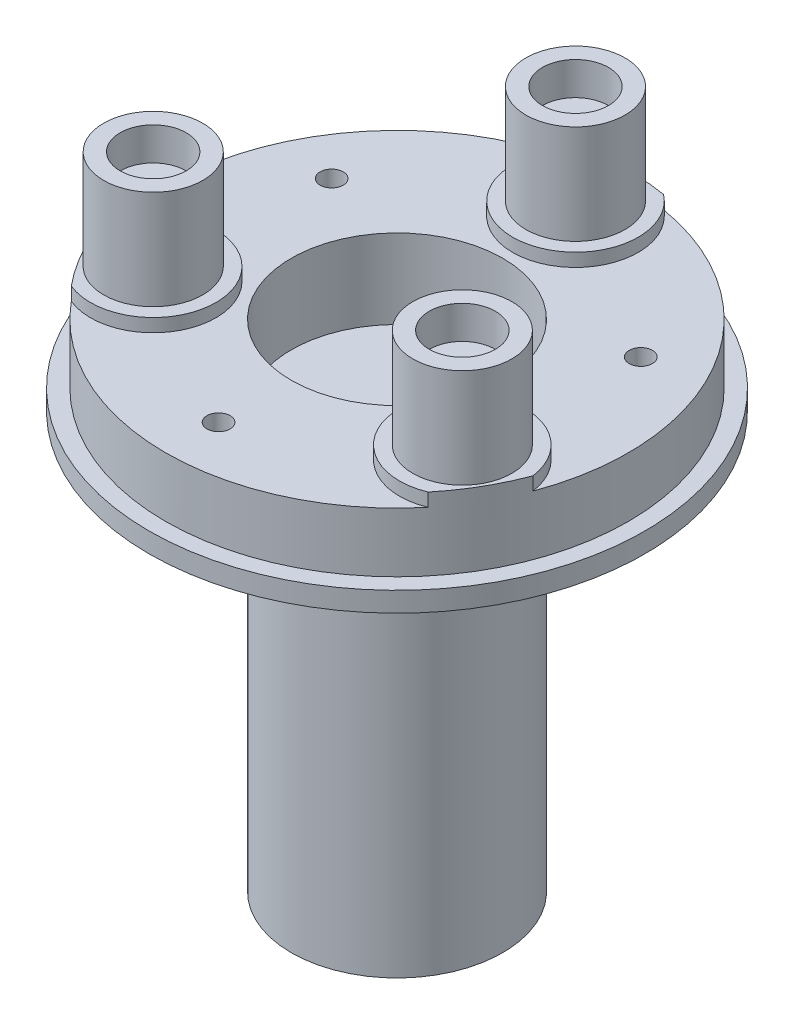
SolidWorks part; units mm, degrees
note: The reader was unsure of these and kept them because the rebuilt part matched: shared geometry of "Sketch1<3>".
ref_plane "Front Plane" through (0, 0, 0) normal (0, 0, 1) x (1, 0, 0)
ref_plane "Top Plane" through (0, 0, 0) normal (0, 1, 0) x (1, 0, 0)
ref_plane "Right Plane" through (0, 0, 0) normal (1, 0, 0) x (0, 0, -1)
sketch "Sketch1" plane through (0, 0, 0) normal (0, 1, 0) x (1, 0, 0)
  line L0 (0, 0) -> (0, 44.6523) construction
  circle A4 centre (0, 0) radius 37.5
  circle A5 centre (0, 0) radius 35
  arc A6 (-10.4425, 33.4059) -> (10.4425, 33.4059) centre (0, 30) ccw
  circle A7 centre (0, 0) radius 35
  arc A8 (34.1516, -7.6594) -> (23.7091, -25.7465) centre (25.9808, -15) ccw
  arc A9 (-23.7091, -25.7465) -> (-34.1516, -7.6594) centre (-25.9808, -15) ccw
  point P17 (0, 0)
  dimension "D1" = 75
  dimension "D2" = 70
  dimension "D3" = 30
  dimension "D4" = 3
extrude "Boss-Extrude1" add sketch "Sketch1" along normal blind 3 contours A4
extrude "Boss-Extrude2" add sketch "Sketch1<3>" along normal blind 12
sketch "Sketch1<3>" plane through (0, 0, 0) normal (0, 1, 0) x (1, 0, 0) same geometry as "Sketch1"
sketch "Sketch13" plane through (0, 12, 0) normal (0, 1, 0) x (1, 0, 0)
  circle A0 centre (0, 0) radius 16
  dimension "D1" = 32
extrude "Cut-Extrude6" cut sketch "Sketch13" against normal through all
sketch "Sketch24" plane through (0, 12, 0) normal (0, 1, 0) x (1, 0, 0)
  line L0 (0, 0) -> (0, 27.027) construction
  arc A0 (-5.813, 34.5139) -> (5.813, 34.5139) centre (0, 27) ccw
  circle A1 centre (0, 0) radius 35
  arc A2 (32.7964, -12.2227) -> (26.9834, -22.2912) centre (23.3827, -13.5) ccw
  arc A3 (-26.9834, -22.2912) -> (-32.7964, -12.2227) centre (-23.3827, -13.5) ccw
  point P15 (0, 0)
  dimension "D1" = 19
  dimension "D4" = 70
  dimension "D2" = 27
  dimension "D3" = 3
extrude "Boss-Extrude9" add sketch "Sketch24" along normal blind 2
sketch "Sketch25" plane through (0, 14, 0) normal (0, 1, 0) x (1, 0, 0)
  line L0 (0, 0) -> (0, 55.8426) construction
  circle A0 centre (0, 27) radius 7.5
  circle A1 centre (23.3827, -13.5) radius 7.5
  circle A2 centre (-23.3827, -13.5) radius 7.5
  point P11 (0, 0)
  dimension "D2" = 15
  dimension "D1" = 27
  dimension "D3" = 3
extrude "Boss-Extrude10" add sketch "Sketch25" along normal blind 15
sketch "Sketch26" plane through (0, 29, 0) normal (0, 1, 0) x (1, 0, 0)
  line L0 (0, 0) -> (0, 38.3857) construction
  circle A0 centre (0, 27) radius 5
  circle A1 centre (23.3827, -13.5) radius 5
  circle A2 centre (-23.3827, -13.5) radius 5
  point P11 (0, 0)
  dimension "D2" = 10
  dimension "D1" = 27
  dimension "D3" = 3
extrude "Cut-Extrude9" cut sketch "Sketch26" against normal blind 5
hole_wizard "CBORE for M3 Pan Head Machine Screw1" positions "Sketch27" profile "Sketch28" counterbore size "M3" standard "ANSI Metric" end condition through all
sketch "Sketch27" plane through (0, 0, 0) normal (0, -1, 0) x (-1, 0, 0)
  point P0 (0, 27)
  point P9 (23.3827, -13.5)
  point P10 (-23.3827, -13.5)
  dimension "D1" = 27
  dimension "D2" = 3
sketch "Sketch28" plane through (0, 0, -27) normal (1, 0, 0) x (0, 0, -1)
  line L0 (0, 0) -> (0, 29)
  line L1 (0, 29) -> (1.8, 29)
  line L3 (1.8, 29) -> (1.8, 2.4)
  line L4 (3.5, 2.4) -> (1.8, 2.4)
  line L5 (3.5, 2.4) -> (3.5, 0.025)
  line L6 (3.5, 0.025) -> (3.525, 0)
  line L7 (3.525, 0) -> (0, 0)
  line L8 (-3.5, 0.025) -> (-3.525, 0) construction
  line L11 (0, -6.35) -> (0, 107.95) construction
  dimension "Thru Hole Dia." = 3.6
  dimension "Thru Hole Depth" = 29
  dimension "C'Bore Dia." = 7
  dimension "C'Bore Depth" = 2.4
  dimension "Near C'Sink Dia." = 7.05
  dimension "Near C'Sink Angle" = 90
sketch "Sketch29" plane through (0, 12, 0) normal (0, 1, 0) x (1, 0, 0)
  line L0 (0, 0) -> (23.3827, 13.5) construction
  line L1 (0, 0) -> (0, 14.4601) construction
  circle A0 centre (23.3827, 13.5) radius 1.75
  circle A1 centre (0, -27) radius 1.75
  circle A2 centre (-23.3827, 13.5) radius 1.75
  point P11 (0, 0)
  dimension "D3" = 3.5
  dimension "D1" = 60
  dimension "D2" = 27
  dimension "D4" = 3
extrude "Cut-Extrude10" cut sketch "Sketch29" against normal through all
sketch "Sketch30" plane through (0, 0, 0) normal (0, -1, 0) x (1, 0, 0)
  circle A0 centre (0, 0) radius 16
extrude "Boss-Extrude11" add sketch "Sketch30" along normal blind 63 separate body
